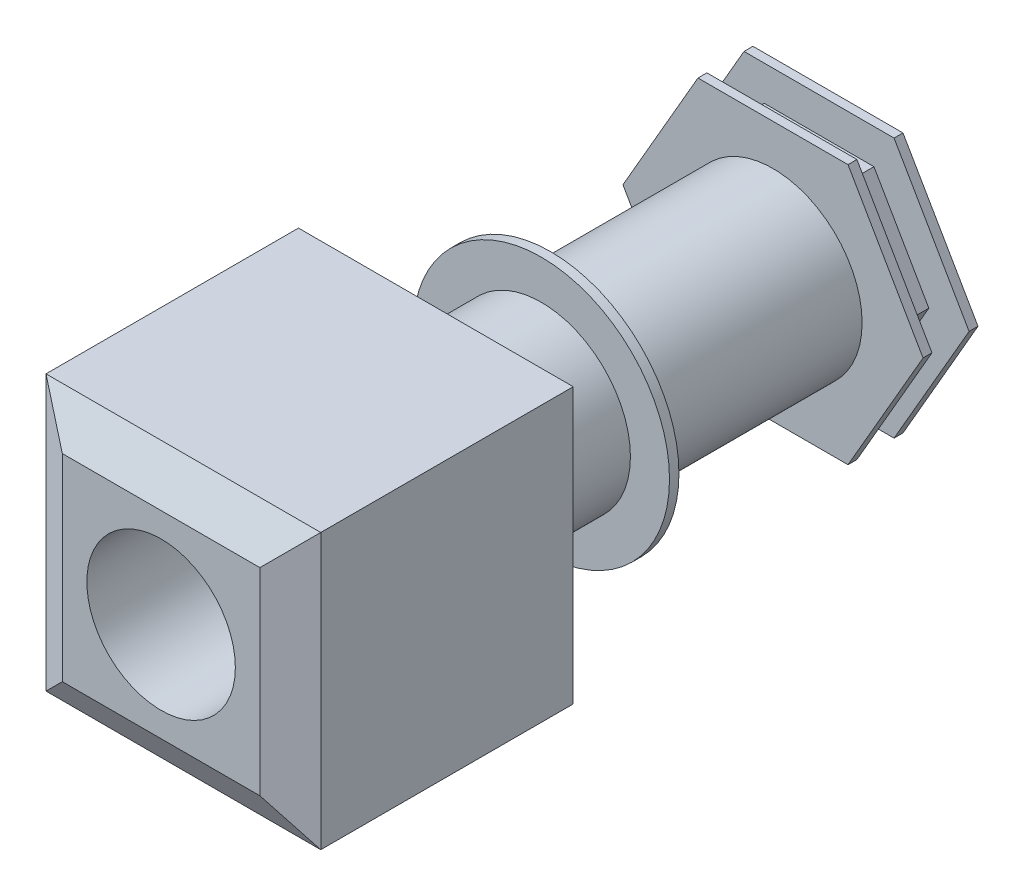
SolidWorks part; units mm, degrees
ref_plane "Front Plane" through (0, 0, 0) normal (0, 0, 1) x (1, 0, 0)
ref_plane "Top Plane" through (0, 0, 0) normal (0, 1, 0) x (1, 0, 0)
ref_plane "Right Plane" through (0, 0, 0) normal (1, 0, 0) x (0, 0, -1)
sketch "Sketch1" plane through (0, 0, 0) normal (0, 0, 1) x (1, 0, 0)
  line L1 (202.0726, 0) -> (101.0363, 175)
  line L2 (101.0363, 175) -> (-101.0363, 175)
  line L3 (-101.0363, 175) -> (-202.0726, 0)
  line L4 (-202.0726, 0) -> (-101.0363, -175)
  line L5 (-101.0363, -175) -> (101.0363, -175)
  line L6 (101.0363, -175) -> (202.0726, 0)
  circle A0 centre (0, 0) radius 175 construction
extrude "Boss-Extrude1" add sketch "Sketch1" along normal blind 12
sketch "Sketch2" plane through (0, 0, 12) normal (0, 0, 1) x (1, 0, 0)
  line L1 (147.8875, 0) -> (73.9437, 128.0743)
  line L2 (73.9437, 128.0743) -> (-73.9437, 128.0743)
  line L3 (-73.9437, 128.0743) -> (-147.8875, 0)
  line L4 (-147.8875, 0) -> (-73.9437, -128.0743)
  line L5 (-73.9437, -128.0743) -> (73.9437, -128.0743)
  line L6 (73.9437, -128.0743) -> (147.8875, 0)
  circle A0 centre (0, 0) radius 128.0743 construction
extrude "Boss-Extrude2" add sketch "Sketch2" along normal blind 50
sketch "Sketch3" plane through (0, 0, 62) normal (0, 0, 1) x (1, 0, 0)
  line L1 (202.0726, 0) -> (101.0363, 175)
  line L2 (101.0363, 175) -> (-101.0363, 175)
  line L3 (-101.0363, 175) -> (-202.0726, 0)
  line L4 (-202.0726, 0) -> (-101.0363, -175)
  line L5 (-101.0363, -175) -> (101.0363, -175)
  line L6 (101.0363, -175) -> (202.0726, 0)
  circle A0 centre (0, 0) radius 175 construction
extrude "Boss-Extrude3" add sketch "Sketch3" along normal blind 12
sketch "Sketch4" plane through (0, 0, 74) normal (0, 0, 1) x (1, 0, 0)
  circle A0 centre (0, 0) radius 120
extrude "Boss-Extrude4" add sketch "Sketch4" along normal blind 300
sketch "Sketch5" plane through (0, 0, 374) normal (0, 0, 1) x (1, 0, 0)
  circle A0 centre (0, 0) radius 172.6469
extrude "Boss-Extrude5" add sketch "Sketch5" along normal blind 12
chamfer "Chamfer1" distance 10 angle 80 1 edges at (120, 0, 374) first distance on face at (120, 0, 374)
sketch "Sketch6" plane through (0, 0, 386) normal (0, 0, 1) x (1, 0, 0)
  circle A0 centre (0, 0) radius 120
extrude "Boss-Extrude6" add sketch "Sketch6" along normal blind 130
sketch "Sketch8" plane through (0, 0, 516) normal (0, 0, 1) x (1, 0, 0)
  circle A0 centre (0, 0) radius 172.6469
extrude "Boss-Extrude7" add sketch "Sketch8" along normal blind 12
chamfer "Chamfer2" distance 6 angle 70 1 edges at (120, 0, 516) first distance on face at (120, 0, 516)
sketch "Sketch9" plane through (0, 0, 528) normal (0, 0, 1) x (1, 0, 0)
  line L1 (-185, 185) -> (185, 185)
  line L2 (-185, 185) -> (-185, -185)
  line L3 (-185, -185) -> (185, -185)
  line L4 (185, 185) -> (185, -185)
  line L5 (-185, 185) -> (185, -185) construction
  line L6 (-185, -185) -> (185, 185) construction
  point P0 (0, 0)
extrude "Boss-Extrude8" add sketch "Sketch9" along normal blind 370
sketch "Sketch10" plane through (0, 0, 898) normal (0, 0, 1) x (1, 0, 0)
  circle A0 centre (0, 0) radius 100
extrude "Cut-Extrude1" cut sketch "Sketch10" against normal blind 900
chamfer "Chamfer3" distance 30 angle 60 4 edges at (185, 0, 898) (0, -185, 898) (-185, 0, 898) (0, 185, 898) first distance on face at (185, 0, 713) first distance on face at (0, -185, 713) first distance on face at (-185, 0, 713) first distance on face at (0, 185, 713)
